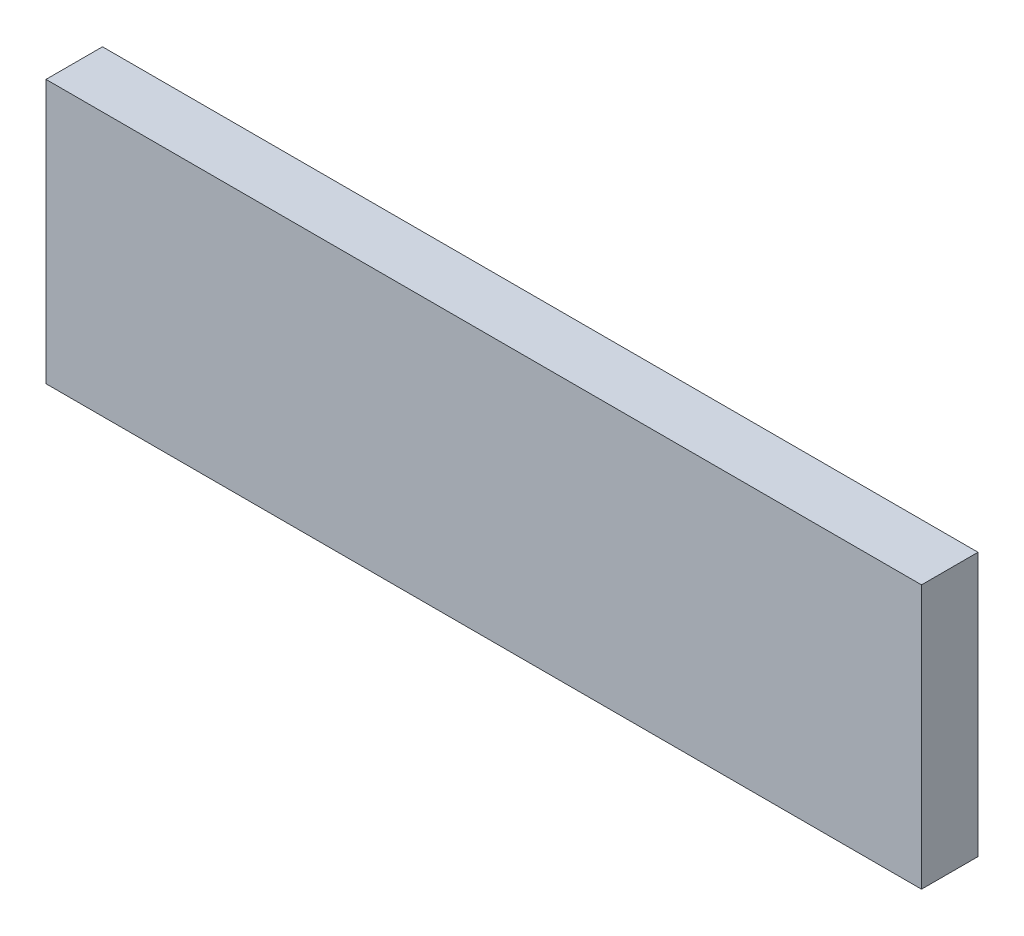
SolidWorks part; units mm, degrees
material "Cedar"
ref_plane "Front Plane" through (0, 0, 0) normal (0, 0, 1) x (1, 0, 0)
ref_plane "Top Plane" through (0, 0, 0) normal (0, 1, 0) x (1, 0, 0)
ref_plane "Right Plane" through (0, 0, 0) normal (1, 0, 0) x (0, 0, -1)
sketch "Sketch1" plane through (0, 0, 0) normal (1, 0, 0) x (0, 0, -1)
  line L1 (-9.525, -44.45) -> (9.525, -44.45)
  line L2 (-9.525, -44.45) -> (-9.525, 44.45)
  line L3 (-9.525, 44.45) -> (9.525, 44.45)
  line L4 (9.525, -44.45) -> (9.525, 44.45)
  line L5 (-9.525, -44.45) -> (9.525, 44.45) construction
  line L6 (-9.525, 44.45) -> (9.525, -44.45) construction
  point P0 (0, 0)
  dimension "D1" = 88.9
  dimension "D2" = 19.05
extrude "Boss-Extrude1" add sketch "Sketch1" along normal blind 295.275
